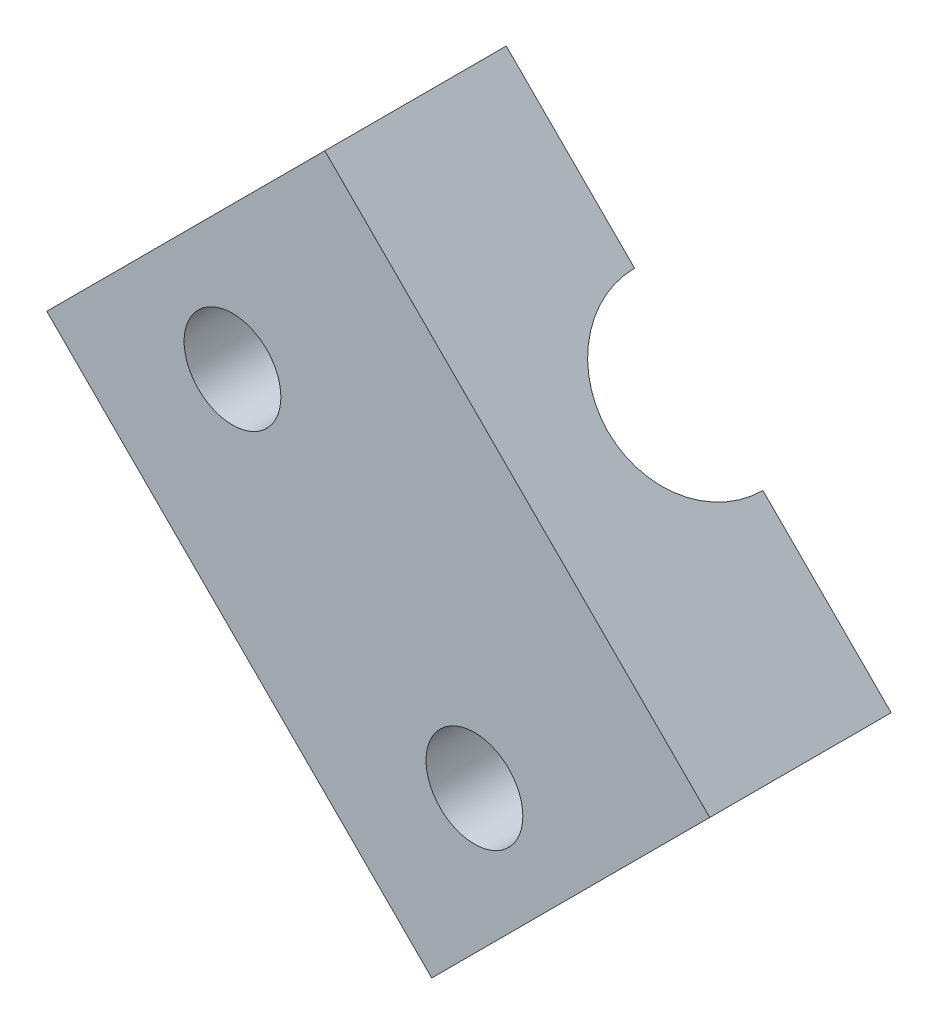
SolidWorks part; units mm, degrees
ref_plane "前视基准面" through (0, 0, 0) normal (0, 0, 1) x (1, 0, 0)
ref_plane "上视基准面" through (0, 0, 0) normal (0, 1, 0) x (1, 0, 0)
ref_plane "右视基准面" through (0, 0, 0) normal (1, 0, 0) x (0, 0, -1)
ref_axis "基准轴1" through (0, 0, 55) along (0, 0, -1)
ref_plane "基准面4" through (0, 0, 0) normal (0.7071, 0.7071, 0) x (0, 0, -1)
sketch "草图3" plane through (0, 0, 0) normal (0.7071, 0.7071, 0) x (0, 0, -1)
  line L0 (0, -9) -> (4, -9) construction
  line L1 (0, 9) -> (-6, 9)
  line L2 (0, 9) -> (0, -9)
  line L3 (0, -9) -> (-6, -9)
  line L4 (-6, 9) -> (-6, -9)
  circle A0 centre (0, 0) radius 3
  dimension "D3" = 6
  dimension "D1" = 0
  dimension "D2" = 6
extrude "凸台-拉伸1" add sketch "草图3" along normal blind 13 contours A0 L2 L1 L4 L3 region at (0, 0, 3.2601)
sketch "草图5" plane through (0, 0, 0) normal (-0.7071, -0.7071, 0) x (0, 0, 1)
  line L0 (0, -3) -> (0, 3)
  circle A0 centre (0, 0) radius 3
  circle A1 centre (0, 0) radius 1
  arc M1 (0, 3) -> (0, -3) centre (0, 0) cw
  dimension "D1" = 2
extrude "凸台-拉伸2" add sketch "草图5" against normal blind 3 contours A1 L0 M1 region at (0, 0, 1.3793)
sketch "草图4" plane through (0, 0, 6) normal (0, 0, 1) x (1, 0, 0)
  line L1 (-6.364, 6.364) -> (6.364, -6.364) construction
  circle A0 centre (-0.224, 7.776) radius 1.6
  circle A1 centre (7.776, -0.224) radius 1.6
  dimension "D1" = 5.34
  dimension "D2" = 5.34
extrude "切除-拉伸1" cut sketch "草图4" against normal blind 10
